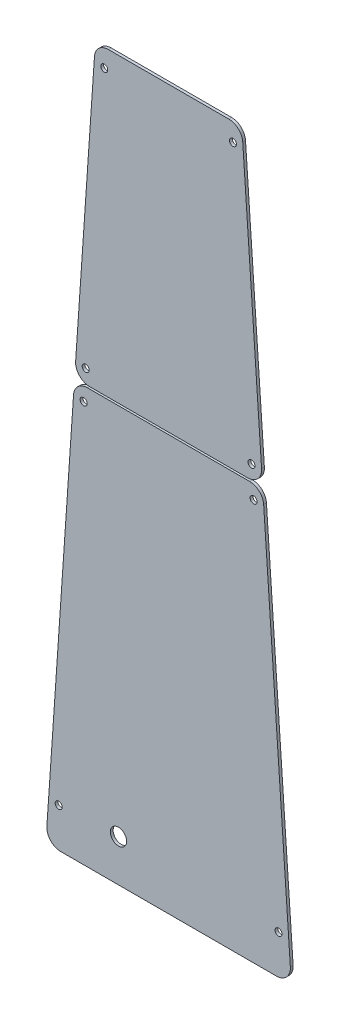
SolidWorks part; units mm, degrees
material "Acrylic (Medium-high impact)"
ref_plane "Front Plane" through (0, 0, 0) normal (0, 0, 1) x (1, 0, 0)
ref_plane "Top Plane" through (0, 0, 0) normal (0, 1, 0) x (1, 0, 0)
ref_plane "Right Plane" through (0, 0, 0) normal (1, 0, 0) x (0, 0, -1)
sketch "Sketch1" plane through (0, 0, 0) normal (0, 0, 1) x (1, 0, 0)
  line L0 (0, 0) -> (0, 515) construction
  line L1 (-52.5, 515) -> (52.5, 515)
  line L2 (52.5, 515) -> (88, 0)
  line L3 (88, 0) -> (-88, 0)
  line L4 (-52.5, 515) -> (-88, 0)
  circle A0 centre (46.1289, 502) radius 2.5
  circle A1 centre (78.7993, 28.05) radius 2.5
  circle A2 centre (-46.1289, 502) radius 2.5
  circle A3 centre (-78.7993, 28.05) radius 2.5
  dimension "D6" = 5
  dimension "D9" = 5
  dimension "D1" = 515
  dimension "D2" = 176
  dimension "D3" = 105
  dimension "D4" = 7.25
  dimension "D5" = 13
  dimension "D7" = 28.05
  dimension "D8" = 7.25
extrude "Boss-Extrude1" add sketch "Sketch1" along normal blind 2 contours L3 L0 L1 L4 A3 A2 | L0 L3 L2 L1 A1 A0 region at (-35.8436, 235.7808, 0) region at (35.8436, 235.7808, 0)
sketch "Sketch2" plane through (0, 0, 2) normal (0, 0, 1) x (1, 0, 0)
  line L1 (39.75, 45.75) -> (-19.75, 45.75)
  line L2 (39.75, 45.75) -> (39.75, 74.25)
  line L3 (39.75, 74.25) -> (-19.75, 74.25)
  line L4 (-19.75, 45.75) -> (-19.75, 74.25)
  line L5 (39.75, 45.75) -> (-19.75, 74.25) construction
  line L6 (39.75, 74.25) -> (-19.75, 45.75) construction
  line L8 (46, 0) -> (26, 0)
  line L9 (46, 0) -> (46, 15)
  line L10 (46, 15) -> (26, 15)
  line L11 (26, 0) -> (26, 15)
  line L12 (88, 0) -> (-88, 0) construction
  point P0 (10, 60)
  dimension "D1" = 28.5
  dimension "D2" = 59.5
  dimension "D3" = 60
  dimension "D4" = 10
  dimension "D5" = 20
  dimension "D6" = 26
  dimension "D7" = 15
extrude "Cut-Extrude1" [suppressed] cut sketch "Sketch2" against normal blind 2
sketch "Sketch3" plane through (0, 0, 2) normal (0, 0, 1) x (1, 0, 0)
  line L0 (10, 30) -> (10, 60) construction
  line L1 (-49, 0) -> (6, 0)
  line L2 (-49, 0) -> (-49, 15)
  line L3 (-49, 15) -> (6, 15)
  line L4 (6, 0) -> (6, 15)
  line L7 (10, 30) -> (60, 30) construction
  circle A14 centre (10, 30) radius 2.5
  circle A15 centre (17.5, 30) radius 2.5
  circle A16 centre (25, 30) radius 2.5
  circle A17 centre (32.5, 30) radius 2.5
  circle A18 centre (40, 30) radius 2.5
  circle A19 centre (47.5, 30) radius 2.5
  circle A20 centre (55, 30) radius 2.5
  circle A21 centre (17.5, 37.5) radius 2.5
  circle A22 centre (25, 37.5) radius 2.5
  circle A23 centre (32.5, 37.5) radius 2.5
  circle A24 centre (40, 37.5) radius 2.5
  circle A25 centre (47.5, 37.5) radius 2.5
  circle A26 centre (55, 37.5) radius 2.5
  circle A27 centre (17.5, 45) radius 2.5
  circle A28 centre (25, 45) radius 2.5
  circle A29 centre (32.5, 45) radius 2.5
  circle A30 centre (40, 45) radius 2.5
  circle A31 centre (47.5, 45) radius 2.5
  circle A32 centre (55, 45) radius 2.5
  circle A33 centre (17.5, 52.5) radius 2.5
  circle A34 centre (25, 52.5) radius 2.5
  circle A35 centre (32.5, 52.5) radius 2.5
  circle A36 centre (40, 52.5) radius 2.5
  circle A37 centre (47.5, 52.5) radius 2.5
  circle A38 centre (55, 52.5) radius 2.5
  circle A39 centre (17.5, 60) radius 2.5
  circle A40 centre (25, 60) radius 2.5
  circle A41 centre (32.5, 60) radius 2.5
  circle A42 centre (40, 60) radius 2.5
  circle A43 centre (47.5, 60) radius 2.5
  circle A44 centre (55, 60) radius 2.5
  circle A45 centre (10, 37.5) radius 2.5
  circle A46 centre (10, 45) radius 2.5
  circle A47 centre (10, 52.5) radius 2.5
  circle A48 centre (10, 60) radius 2.5
  dimension "D7" = 50
  dimension "D6" = 5
  dimension "D1" = 6
  dimension "D2" = 15
  dimension "D3" = 55
  dimension "D4" = 10
  dimension "D5" = 30
  dimension "D8" = 30
  dimension "D10" = 7.5
  dimension "D11" = 7.5
  dimension "D9" = 5
extrude "Cut-Extrude2" [suppressed] cut sketch "Sketch3" against normal blind 2
fillet "Fillet1" radius 10 4 edges at (-88, 0, 1) (88, 0, 1) (52.5, 515, 1) (-52.5, 515, 1)
sketch "Sketch4" plane through (0, 0, 0) normal (0, 0, -1) x (-1, 0, 0)
  line L0 (43.1656, 515) -> (-43.1656, 515) construction
  line L1 (0, 515) -> (0, 520) construction
  line L2 (-19.3649, 515) -> (19.3649, 515)
  arc A0 (-19.3649, 515) -> (19.3649, 515) centre (0, 520) ccw
  dimension "D1" = 20
  dimension "D2" = 5
extrude "Cut-Extrude3" [suppressed] cut sketch "Sketch4" against normal blind 10
fillet "Fillet2" [suppressed] radius 10
sketch "Sketch5" plane through (0, 0, 2) normal (0, 0, 1) x (1, 0, 0)
  line L0 (0, 0) -> (0, 110) construction
  line L1 (-48.75, 275.9812) -> (51.25, 275.9812)
  line L2 (-48.75, 275.9812) -> (-48.75, 157.7884)
  line L3 (-51.25, 110) -> (51.25, 110)
  line L4 (51.25, 275.9812) -> (51.25, 110)
  line L5 (-48.75, 157.7884) -> (-51.25, 140)
  line L6 (-51.25, 140) -> (-51.25, 110)
  line L8 (51.25, 192.4812) -> (-48.75, 192.4812) construction
  circle A0 centre (57.25, 270.9812) radius 2
  circle A1 centre (-58.75, 270.9812) radius 2
  circle A2 centre (-58.75, 113.9812) radius 2
  circle A3 centre (57.25, 113.9812) radius 2
  dimension "D7" = 6
  dimension "D8" = 4
  dimension "D9" = 10
  dimension "D11" = 4
  dimension "D1" = 110
  dimension "D2" = 102.5
  dimension "D3" = 166
  dimension "D4" = 2.5
  dimension "D5" = 8
  dimension "D6" = 30
  dimension "D10" = 5
  dimension "D12" = 83.5
extrude "Cut-Extrude4" [suppressed] cut sketch "Sketch5" against normal blind 10
sketch "Sketch6" plane through (0, 0, 0) normal (0, 0, -1) x (-1, 0, 0)
  line L0 (-67.3893, 299) -> (67.3893, 299)
  line L1 (-53.1419, 505.6877) -> (-87.2633, 10.6877) construction
  line L2 (53.1419, 505.6877) -> (87.2633, 10.6877) construction
  line L3 (-67.4927, 297.5) -> (67.4927, 297.5)
  line L4 (67.4927, 297.5) -> (67.3893, 299)
  line L5 (-67.3893, 299) -> (-67.4927, 297.5)
  line L6 (-78.7993, 28.05) -> (-46.1289, 502) construction
  line L7 (0, 515) -> (0, 0) construction
  line L9 (78.7993, 28.05) -> (46.1289, 502) construction
  line L10 (67.3893, 299) -> (67.4927, 297.5)
  circle A0 centre (-60.9148, 287.5) radius 2.5
  circle A1 centre (-59.4328, 309) radius 2.5
  circle A2 centre (-46.1289, 502) radius 2.5 construction
  circle A3 centre (59.4328, 309) radius 2.5
  circle A4 centre (60.9148, 287.5) radius 2.5
  line M16 (87.2633, 10.6877) -> (53.1419, 505.6877)
  line M20 (-53.1419, 505.6877) -> (-87.2633, 10.6877)
  dimension "D3" = 10
  dimension "D1" = 1.5
  dimension "D2" = 297.5
  dimension "D4" = 10
  dimension "D5" = 515
extrude "Cut-Extrude5" cut sketch "Sketch6" against normal blind 10 contours A0 | L3 L0 M20 M16 | A1 | A3 | A4 region at (0, 298.2498, 0) region at (60.9148, 287.5, 0) region at (59.4328, 309, 0) region at (-59.4328, 309, 0) region at (-60.9148, 287.5, 0)
fillet "Fillet3" radius 10 2 edges at (-67.4927, 297.5, 1) (67.4927, 297.5, 1)
fillet "Fillet4" radius 10 2 edges at (-67.3893, 299, 1) (67.3893, 299, 1)
sketch "Sketch7" plane through (0, 0, 2) normal (0, 0, -1) x (-1, 0, 0)
  line L0 (-38.1656, 490) -> (-13.1656, 490) construction
  line L1 (43.1656, 515) -> (-43.1656, 515) construction
  line L2 (-38.1656, 490) -> (-38.1656, 475) construction
  line L11 (-38.1656, 475) -> (-13.1656, 475) construction
  circle A0 centre (-35.6656, 486) radius 2
  circle A1 centre (-35.6656, 480) radius 2
  text T0 "OB15" font "@HYSWLongFangSong" height 5
  dimension "D5" = 4
  dimension "D1" = 25
  dimension "D2" = 25
  dimension "D3" = 5
  dimension "D4" = 5
  dimension "D6" = 4
  dimension "D7" = 6
  dimension "D11" = 25
  dimension "D12" = 15
extrude "Cut-Extrude6" [suppressed] cut sketch "Sketch7" against normal through all both and the other way through all contours A0 | A1
delete or keep bodies "Body-Delete/Keep 1" [suppressed] type delete bodies bodies 119 117 118
sketch "Sketch8" plane through (0, 0, 2) normal (0, 0, 1) x (1, 0, 0)
  line L0 (77.2869, 0) -> (-77.2869, 0) construction
  line L1 (-60, 0) -> (60, 0)
  line L2 (-60, 0) -> (-60, 10)
  line L3 (-60, 10) -> (60, 10)
  line L4 (60, 0) -> (60, 10)
  dimension "D1" = 120
  dimension "D2" = 10
extrude "Cut-Extrude7" [suppressed] cut sketch "Sketch8" against normal blind 10
pattern_linear "LPattern1" [suppressed] count 5 spacing 6 of bodies 113
sketch "Sketch9" [suppressed] plane through (0, 0, 0) normal (0, 0, -1) x (-1, 0, 0)
  line L1 (-26, 0) -> (77.2869, 0) construction
  line L2 (32.4525, 515) -> (-108.8711, 515)
  line L3 (-108.8711, 515) -> (-108.8711, 0)
  line L4 (-108.8711, 0) -> (67.9525, 0)
  line L5 (-25.9808, 515) -> (-43.1656, 515) construction
  line L6 (32.4525, 515) -> (67.9525, 0)
  line L7 (68.1346, 288.1877) -> (87.2633, 10.6877) construction
  line L8 (53.1419, 505.6877) -> (66.6526, 309.6877) construction
  dimension "D1" = 20
extrude "Cut-Extrude8" [suppressed] cut sketch "Sketch9" against normal blind 10
fillet "Fillet5" [suppressed] radius 5
fillet "Fillet6" [suppressed] radius 15
fillet "Fillet7" [suppressed] radius 10
fillet "Fillet8" [suppressed] radius 10
sketch "Sketch10" plane through (0, 0, 2) normal (0, 0, 1) x (1, 0, 0)
  line L0 (-16.3, 485) -> (-16.3, 487) construction
  line L1 (-29.3, 485) -> (-3.3, 485)
  line L2 (-29.3, 485) -> (-29.3, 469)
  line L3 (-29.3, 469) -> (-3.3, 469)
  line L4 (-3.3, 485) -> (-3.3, 469)
  line L5 (-16.3, 469) -> (-16.3, 465) construction
  line L6 (-27.3, 465) -> (-5.3, 465) construction
  line L7 (-27.3, 487) -> (-5.3, 487) construction
  line L8 (0, 0) -> (0, 515) construction
  line L9 (-43.1656, 515) -> (43.1656, 515) construction
  circle A4 centre (-5.3, 465) radius 1.425
  circle A5 centre (-27.3, 465) radius 1.425
  circle A6 centre (-5.3, 487) radius 1.425
  circle A7 centre (-27.3, 487) radius 1.425
  dimension "D9" = 2.85
  dimension "D1" = 26
  dimension "D2" = 16
  dimension "D3" = 22
  dimension "D4" = 22
  dimension "D5" = 2
  dimension "D6" = 4
  dimension "D7" = 3.3
  dimension "D8" = 30
extrude "Cut-Extrude9" [suppressed] cut sketch "Sketch10" against normal through all both and the other way through all
sketch "Sketch11" plane through (0, 0, 2) normal (0, 0, 1) x (1, 0, 0)
  line L0 (0, 0) -> (0, 144.8565) construction
  line L1 (77.2869, 0) -> (-77.2869, 0) construction
  line L3 (0, 30) -> (-85.932, 30) construction
  line L4 (-68.1346, 288.1877) -> (-87.2633, 10.6877) construction
  circle A0 centre (-35.932, 30) radius 5.825
  circle A1 centre (-15.932, 30) radius 5.825
  dimension "D1" = 11.65
  dimension "D2" = 11.65
  dimension "D3" = 50
  dimension "D4" = 20
  dimension "D5" = 30
extrude "Cut-Extrude10" [suppressed] cut sketch "Sketch11" against normal through all both and the other way through all contours A0
extrude "Cut-Extrude11" cut sketch "Sketch11<3>" against normal blind 10 contours A0 region at (-35.932, 30, 2)
sketch "Sketch11<3>" plane through (0, 0, 2) normal (0, 0, 1) x (1, 0, 0) same geometry as "Sketch11"
sketch "Sketch12" [suppressed] plane through (0, 0, 0) normal (0, 0, -1) x (-1, 0, 0)
  line L6 (-56.6763, 299) -> (56.6763, 299)
  line L7 (66.6526, 309.6877) -> (53.1419, 505.6877)
  line L8 (43.1656, 515) -> (-43.1656, 515)
  line L9 (-53.1419, 505.6877) -> (-66.6526, 309.6877)
  line L10 (-56.6763, 299) -> (56.6763, 299)
  line L11 (66.6526, 309.6877) -> (53.1419, 505.6877)
  line L12 (43.1656, 515) -> (-43.1656, 515)
  line L13 (-53.1419, 505.6877) -> (-66.6526, 309.6877)
  circle A0 centre (-59.4328, 309) radius 2.5 construction
  circle A1 centre (59.4328, 309) radius 2.5 construction
  circle A2 centre (46.1289, 502) radius 2.5 construction
  circle A3 centre (-46.1289, 502) radius 2.5 construction
  arc A4 (56.6763, 299) -> (66.6526, 309.6877) centre (56.6763, 309) ccw
  arc A5 (53.1419, 505.6877) -> (43.1656, 515) centre (43.1656, 505) ccw
  arc A6 (-43.1656, 515) -> (-53.1419, 505.6877) centre (-43.1656, 505) ccw
  arc A7 (-66.6526, 309.6877) -> (-56.6763, 299) centre (-56.6763, 309) ccw
  arc A8 (56.6763, 299) -> (66.6526, 309.6877) centre (56.6763, 309) ccw
  arc A9 (53.1419, 505.6877) -> (43.1656, 515) centre (43.1656, 505) ccw
  arc A10 (-43.1656, 515) -> (-53.1419, 505.6877) centre (-43.1656, 505) ccw
  arc A11 (-66.6526, 309.6877) -> (-56.6763, 299) centre (-56.6763, 309) ccw
  circle A12 centre (-59.4328, 309) radius 2.5
  circle A13 centre (59.4328, 309) radius 2.5
  circle A14 centre (46.1289, 502) radius 2.5
  circle A15 centre (-46.1289, 502) radius 2.5
  text T0 "<b><i>Jeremy</i></b>" font "Harlow Solid Italic" height 15
  dimension "D1" = 0
